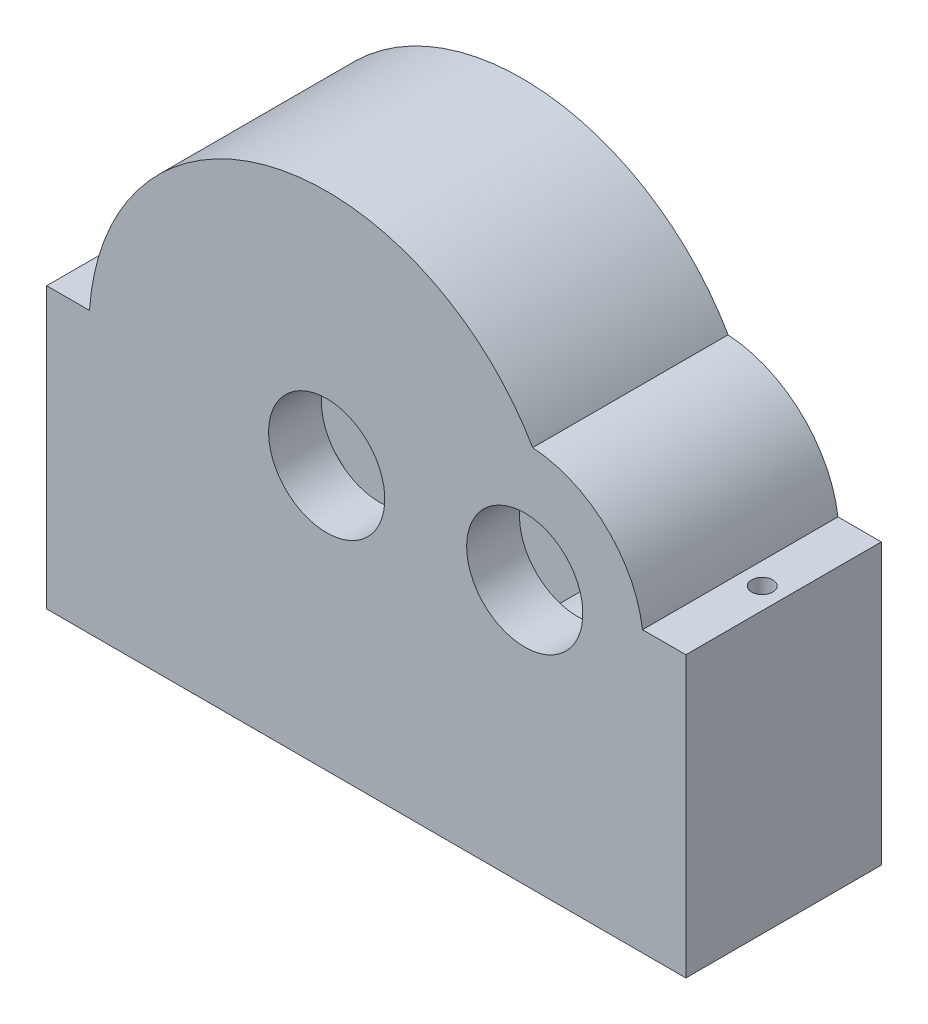
SolidWorks part; units mm, degrees
ref_plane "Front Plane" through (0, 0, 0) normal (0, 0, 1) x (1, 0, 0)
ref_plane "Top Plane" through (0, 0, 0) normal (0, 1, 0) x (1, 0, 0)
ref_plane "Right Plane" through (0, 0, 0) normal (1, 0, 0) x (0, 0, -1)
sketch "Sketch1" plane through (0, 0, 0) normal (0, 0, 1) x (1, 0, 0)
  line L0 (-18.75, 0) -> (18.75, 0)
  line L1 (-73.75, -5) -> (-73.75, -55)
  line L3 (-73.75, -5) -> (-73.75, 5)
  line L4 (-73.75, 5) -> (-63.4714, 5)
  line L10 (40.6874, 5) -> (51.25, 5)
  line L11 (51.25, -5) -> (51.25, 5)
  line L14 (51.25, -5) -> (51.25, -55)
  line L15 (51.25, -55) -> (-73.75, -55)
  circle A0 centre (18.75, 0) radius 7.5
  circle A1 centre (-18.75, 0) radius 30
  arc A2 (20.25, 22.4499) -> (20.25, -22.4499) centre (-18.75, 0) ccw
  arc A3 (20.25, -22.4499) -> (20.25, 22.4499) centre (18.75, 0) ccw
  circle A5 centre (18.75, 0) radius 22.5 construction
  circle A6 centre (-18.75, 0) radius 45 construction
  point P4 (0, 0)
  point P7 (-63.75, 0)
  point P10 (31.25, 0)
  point P13 (16.25, 0)
  point P19 (41.25, 0)
  dimension "D1" = 37.5
  dimension "D2" = 60
  dimension "D3" = 15
  dimension "D4" = 15
  dimension "D5" = 15
extrude "Boss-Extrude2" add sketch "Sketch1" along normal blind 27 contours A3 A2 A1 A0 | A1 | A0 region at (-27.6498, 42.6994, 0) region at (18.75, -7.2879, 0) region at (-47.9015, 0, 0)
shell "Shell5" thickness 10 removed face at (-11.25, 0, 0)
sketch "Sketch2" plane through (0, 0, 17) normal (0, 0, -1) x (-1, 0, 0)
  line L0 (-18.75, 0) -> (18.75, 0) construction
  circle A0 centre (-18.75, 0) radius 4
  circle A1 centre (18.75, 0) radius 4
  point P4 (0, 0)
sketch "Sketch4" plane through (0, 0, 0) normal (0, 0, -1) x (-1, 0, 0)
  arc A0 (-20.25, 22.4499) -> (-20.25, -22.4499) centre (-18.75, 0) ccw construction
  arc A1 (-20.25, -22.4499) -> (-20.25, 22.4499) centre (18.75, 0) ccw construction
  arc A4 (-20.25, 22.4499) -> (-20.25, -22.4499) centre (-18.75, 0) ccw
  arc A5 (-20.25, -22.4499) -> (-20.25, 22.4499) centre (18.75, 0) ccw
extrude "Boss-Extrude3" add sketch "Sketch4" along normal blind 10
sketch "Sketch5" plane through (0, 0, -10) normal (0, 0, -1) x (-1, 0, 0)
  line L0 (-18.75, 0) -> (18.75, 0) construction
  line L1 (-18.75, 0) -> (18.75, 0)
  circle A6 centre (-18.75, 0) radius 11
  circle A7 centre (18.75, 0) radius 11
extrude "Cut-Extrude2" cut sketch "Sketch5" against normal through all contours A6 | A7 region at (-18.75, 10.6889, -10) region at (29.4389, 0, -10)
sketch "Sketch8" plane through (0, 0, -10) normal (0, 0, -1) x (-1, 0, 0)
  line L0 (-41.25, 0) -> (63.75, 0) construction
  line L1 (11.25, 0) -> (11.25, 61.6014) construction
  line L2 (-41.25, 0) -> (-41.25, -50)
  line L3 (-41.25, -50) -> (63.75, -50)
  line L4 (63.75, -50) -> (63.75, 0)
  arc A0 (-20.25, 22.4499) -> (-20.25, -22.4499) centre (-18.75, 0) ccw construction
  arc A1 (-20.25, -22.4499) -> (-20.25, 22.4499) centre (18.75, 0) ccw construction
  arc A2 (-20.25, -22.4499) -> (63.75, 0) centre (18.75, 0) ccw
  arc A3 (-41.25, 0) -> (-20.25, -22.4499) centre (-18.75, 0) ccw
extrude "Boss-Extrude4" add sketch "Sketch8" against normal up to surface (37 mm away) up to face at (7.75, 0, 27)
sketch "Sketch9" plane through (0, 0, 0) normal (0, 1, 0) x (1, 0, 0)
  line L0 (-63.75, -8.5) -> (41.25, -8.5) construction
  line L5 (41.25, -27) -> (41.25, 10) construction
  line L6 (-11.25, -8.5) -> (-11.25, 40.864) construction
  line L11 (-63.75, -8.5) -> (-58.75, -8.5) construction
  line L12 (-58.75, -8.5) -> (-58.75, 10)
  line L13 (20.25, 10) -> (-63.75, 10) construction
  line L14 (-58.75, 10) -> (-71.75, 10)
  line L15 (-71.75, 10) -> (-71.75, -27)
  line L16 (-71.75, -27) -> (-58.75, -27)
  line L17 (-63.75, -27) -> (20.25, -27) construction
  line L18 (-58.75, -27) -> (-58.75, -8.5)
  line L19 (36.25, -27) -> (36.25, -8.5)
  line L20 (49.25, -27) -> (36.25, -27)
  line L21 (49.25, 10) -> (49.25, -27)
  line L22 (36.25, 10) -> (49.25, 10)
  line L23 (36.25, -8.5) -> (36.25, 10)
extrude "Boss-Extrude5" add sketch "Sketch9" along normal blind 3 and the other way up to surface (50 mm away) contours L16 L18 L12 L14 L15 | L23 L19 L20 L21 L22 region at (-65.25, 0, 8.5) region at (42.75, 0, 8.5) other way up to face at (-11.25, -50, 8.5)
sketch "Sketch10" plane through (0, 3, 0) normal (0, 1, 0) x (1, 0, 0)
  line L0 (-71.75, -8.5) -> (49.25, -8.5) construction
  line L1 (-71.75, 10) -> (-71.75, -27) construction
  line L2 (49.25, 10) -> (49.25, -27) construction
  line L3 (-11.25, -8.5) -> (-11.25, 28.9746) construction
  line L4 (-71.75, -8.5) -> (-63.6499, -8.5)
  line L5 (-63.6499, 10) -> (-63.6499, -27) construction
  circle A0 centre (-67.6999, -8.5) radius 2
  circle A1 centre (45.1999, -8.5) radius 2
extrude "Cut-Extrude3" cut sketch "Sketch10" against normal blind 10 contours A1 | A0
